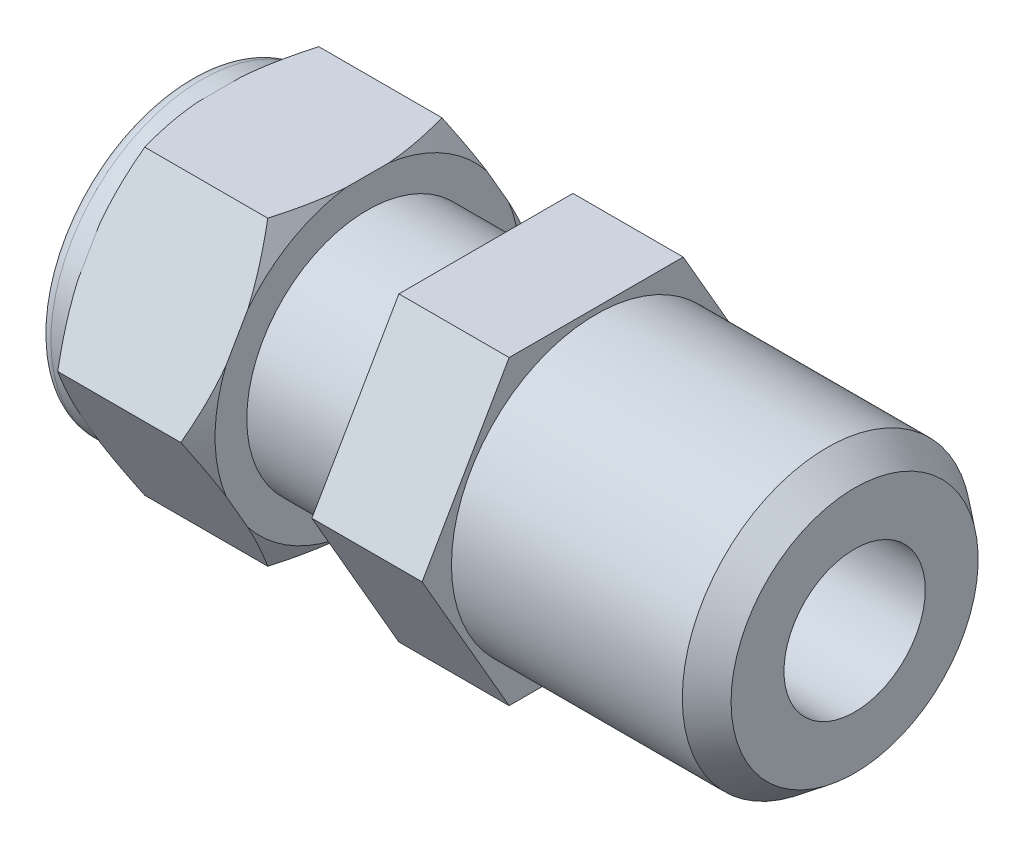
SolidWorks part; units mm, degrees
ref_plane "Front" through (0, 0, 0) normal (0, 0, 1) x (1, 0, 0)
ref_plane "Top" through (0, 0, 0) normal (0, 1, 0) x (1, 0, 0)
ref_plane "Right" through (0, 0, 0) normal (1, 0, 0) x (0, 0, -1)
other "Configuration Table"
sketch "BodySch" plane through (0, 0, 0) normal (0, 0, 1) x (1, 0, 0)
  line L0 (-103.6847, 0) -> (134.0726, 0) construction
  line L1 (-49.022, 0) -> (-49.022, 11.1125)
  line L2 (-49.022, 11.1125) -> (-41.3766, 11.1125)
  line L3 (-41.3766, 11.1125) -> (-41.3766, 8.89)
  line L4 (-41.3766, 8.89) -> (-27.178, 8.89)
  line L5 (-27.178, 8.89) -> (-27.178, 10.668)
  line L6 (-27.178, 10.668) -> (-2.0334, 10.668)
  line L7 (0, 9.1077) -> (-2.0334, 10.668)
  line L8 (-49.022, 0) -> (0, 0)
  line L9 (0, 9.1077) -> (0, 0)
  line L10 (-19.05, 10.668) -> (-19.05, 0) construction
  dimension "D1" = 37.5
  dimension "L4" = 19.05
revolve "Body" add sketch "BodySch" angle 360 about L0
sketch "Hex1Sch_G" plane through (-41.3766, 0, 0) normal (1, 0, 0) x (0, 0, -1)
  line L1 (12.8316, 0) -> (6.4158, 11.1125)
  line L2 (6.4158, 11.1125) -> (-6.4158, 11.1125)
  line L3 (-6.4158, 11.1125) -> (-12.8316, 0)
  line L4 (-12.8316, 0) -> (-6.4158, -11.1125)
  line L5 (-6.4158, -11.1125) -> (6.4158, -11.1125)
  line L6 (6.4158, -11.1125) -> (12.8316, 0)
  circle A0 centre (0, 0) radius 11.1125 construction
  dimension "G" = 22.225
extrude "Hex1" add sketch "Hex1Sch_G" along normal mid plane 10.922
sketch "PlaneCSch" plane through (0, 0, 0) normal (0, 0, 1) x (1, 0, 0)
  line L0 (-27.178, 10.668) -> (-27.178, -10.668) construction
  point P0 (-27.178, 5.1403)
fillet "BodyFillet" radius 0.889 1 edges at (-49.022, 0, 11.1125)
ref_plane "PlaneC" through (-27.178, 0, 0) normal (-1, 0, 0) x (0, 0, 1)
sketch "HexfilletSch" plane through (0, 0, 0) normal (0, 1, 0) x (1, 0, 0)
  line L0 (-46.8376, 11.2277) -> (-45.9116, 12.8316)
  line L1 (-46.8376, 12.8316) -> (-46.8376, 9.6237) construction
  line L2 (-35.9156, 12.8316) -> (-46.8376, 12.8316) construction
  line L3 (-35.9156, 12.8316) -> (-35.9156, 6.4158) construction
  line L5 (-35.9156, 11.2277) -> (-36.8416, 12.8316)
  line L6 (-46.8376, 11.2277) -> (-46.8376, 12.8316)
  line L7 (-35.9156, 11.2277) -> (-35.9156, 12.8316)
  line L8 (-46.8376, 12.8316) -> (-45.9116, 12.8316)
  line L9 (-41.9948, 0) -> (5.5242, 0) construction
  line L10 (-103.6847, 0) -> (134.0726, 0) construction
  line L12 (-35.9156, 12.8316) -> (-36.8416, 12.8316)
  dimension "D1" = 60
  dimension "D2" = 30
revolve "Hexfillet" cut sketch "HexfilletSch" angle 360 about L9
sketch "Hex2Sch_F" plane through (-27.178, 0, 0) normal (-1, 0, 0) x (0, 0, 1)
  line L3 (12.8316, 0) -> (6.4158, 11.1125)
  line L5 (6.4158, 11.1125) -> (-6.4158, 11.1125)
  line L7 (-6.4158, 11.1125) -> (-12.8316, 0)
  line L9 (-12.8316, 0) -> (-6.4158, -11.1125)
  line L11 (-6.4158, -11.1125) -> (6.4158, -11.1125)
  line L12 (6.4158, -11.1125) -> (12.8316, 0)
  circle A2 centre (0, 0) radius 11.1125 construction
  dimension "F" = 22.225
extrude "Hex2" add sketch "Hex2Sch_F" against normal blind 8.128
sketch "DSch" plane through (-49.022, 0, 0) normal (1, 0, 0) x (0, 0, -1)
  circle A0 centre (0, 0) radius 6.35
  dimension "T" = 12.7
extrude "Cut-ExtrudeD" cut sketch "DSch" along normal blind 22.86
sketch "E" plane through (0, 0, 0) normal (1, 0, 0) x (0, 0, -1)
  circle A0 centre (0, 0) radius 5.207
  dimension "E" = 10.414
extrude "Cut-ExtrudeE" cut sketch "E" against normal up to surface (26.162 mm away) up to face at (-26.162, 0, -6.35)
sketch "Sketch1" plane through (0, 0, 0) normal (0, 1, 0) x (1, 0, 0)
  line L0 (-19.05, -10.668) -> (-19.05, 10.668) construction
  line L1 (-26.162, 5.207) -> (-26.162, -5.207) construction
  point P0 (0, 0)
  point P1 (-26.162, 0)
  point P3 (-19.05, 0)
other "CPoint2" parameters "Diameter"=12.7, "StubLength"=0
ref_axis "Axis1" through (-36.162, 0, 0) along (1, 0, 0)
other "CPoint1" parameters "Diameter"=12.7, "StubLength"=0
ref_axis "Axis2" through (10, 0, 0) along (-1, 0, 0)
other "RPoint1"
equation "\"Hex1_middle_point@BodySch\"=\"C@BodySch\"*.35"
equation "\"Depth@Hex1\"=\"C@BodySch\"*.5"
equation "\"Depth@Hex2\"=\"Length@BodySch\"-\"L4@BodySch\"-\"C@BodySch\""
equation "\"Dia_ouside_D1@BodySch\"=\"G@Hex1Sch_G\""
equation "\"D1@BodyFillet\"=\"Dia_ouside_D1@BodySch\"/25"
